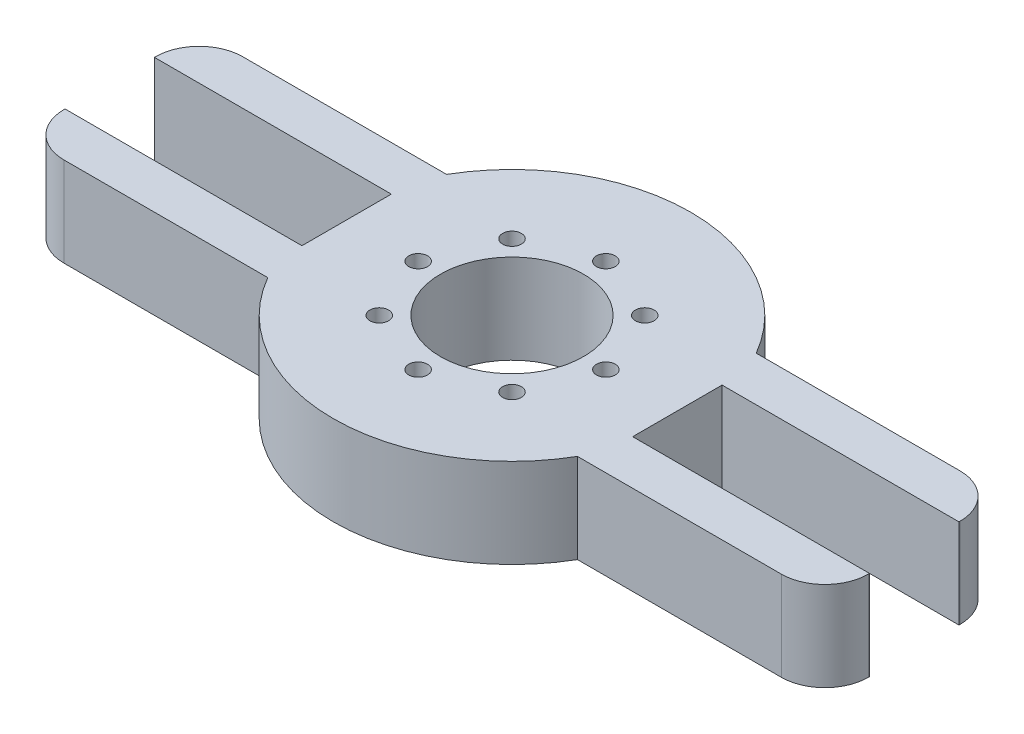
SolidWorks part; units mm, degrees
material "PTFE (general)"
ref_plane "Front Plane" through (0, 0, 0) normal (0, 0, 1) x (1, 0, 0)
ref_plane "Top Plane" through (0, 0, 0) normal (0, 1, 0) x (1, 0, 0)
ref_plane "Right Plane" through (0, 0, 0) normal (1, 0, 0) x (0, 0, -1)
sketch "Sketch1" plane through (0, 0, 0) normal (0, 1, 0) x (1, 0, 0)
  line L0 (34.641, 20) -> (90, 20)
  line L1 (90, 20) -> (90, -20)
  line L2 (90, -20) -> (34.641, -20)
  line L3 (0, -20) -> (0, 20)
  line L4 (0, 20) -> (0, 40)
  line L5 (0, -20) -> (0, -40)
  arc A0 (0, -40) -> (34.641, -20) centre (0, 0) ccw
  arc A1 (34.641, 20) -> (0, 40) centre (0, 0) ccw
  point P5 (0, 0)
  dimension "D1" = 80
  dimension "D2" = 90
  dimension "D3" = 40
extrude "Boss-Extrude1" add sketch "Sketch1" along normal blind 20
sketch "Sketch2" plane through (0, 20, 0) normal (0, 1, 0) x (1, 0, 0)
  line L0 (0, 16) -> (0, -16)
  line L5 (37, 10) -> (90, 10)
  line L7 (90, 10) -> (90, -10)
  line L8 (90, -10) -> (37, -10)
  line L9 (37, -10) -> (37, 10)
  line L10 (90, -20) -> (90, 20) construction
  arc A0 (0, -16) -> (0, 16) centre (0, 0) ccw
  point P6 (37, 0)
  dimension "D1" = 32
  dimension "D2" = 53
  dimension "D3" = 20
extrude "Cut-Extrude1" cut sketch "Sketch2" against normal up to surface (20 mm away) up to face at (42.4402, 0, 0)
fillet "Fillet1" radius 9.75 2 edges at (90, 10, 20) (90, 10, -20)
sketch "Sketch3" plane through (0, 0, -20) normal (0, 0, -1) x (-1, 0, 0)
  line L0 (0, 20) -> (0, 0) construction
  circle A0 centre (-40, 10) radius 2.5
  circle A1 centre (-50, 10) radius 2.5
  circle A2 centre (-60, 10) radius 2.5
  circle A3 centre (-70, 10) radius 2.5
  circle A4 centre (-80, 10) radius 2.5
  circle A5 centre (-90, 10) radius 2.5
  circle A6 centre (-100, 10) radius 2.5
  point P4 (0, 10)
  dimension "D2" = 5
  dimension "D1" = 40
  dimension "D3" = 7
extrude "Cut-Extrude2" [suppressed] cut sketch "Sketch3" against normal up to surface (40 mm away)
mirror "Mirror4" about plane through (0, 0, 0) normal (1, 0, 0) of "Boss-Extrude1", "Cut-Extrude1", "Fillet1", "Cut-Extrude2"
sketch "Sketch4" plane through (0, 20, 0) normal (0, 1, 0) x (1, 0, 0)
  circle A0 centre (21, 0) radius 2.1
  circle A1 centre (14.8492, -14.8492) radius 2.1
  circle A2 centre (0, -21) radius 2.1
  circle A3 centre (-14.8492, -14.8492) radius 2.1
  circle A4 centre (-21, 0) radius 2.1
  circle A5 centre (-14.8492, 14.8492) radius 2.1
  circle A6 centre (0, 21) radius 2.1
  circle A7 centre (14.8492, 14.8492) radius 2.1
  point P19 (0, 0)
  dimension "D2" = 4.2
  dimension "D1" = 21
  dimension "D3" = 8
extrude "Cut-Extrude3" cut sketch "Sketch4" against normal up to surface (20 mm away) up to face at (0, 0, 0)
sketch "Sketch5" plane through (0, 20, 0) normal (0, 1, 0) x (1, 0, 0)
  line L0 (0, 40) -> (0, -40) construction
  line L1 (-37, 0) -> (37, 0) construction
  line L6 (-37, 10) -> (-37, -10) construction
  line L7 (37, 10) -> (37, -10) construction
  arc A2 (34.641, 20) -> (-34.641, 20) centre (0, 0) ccw construction
  arc A3 (-34.641, -20) -> (34.641, -20) centre (0, 0) ccw construction
